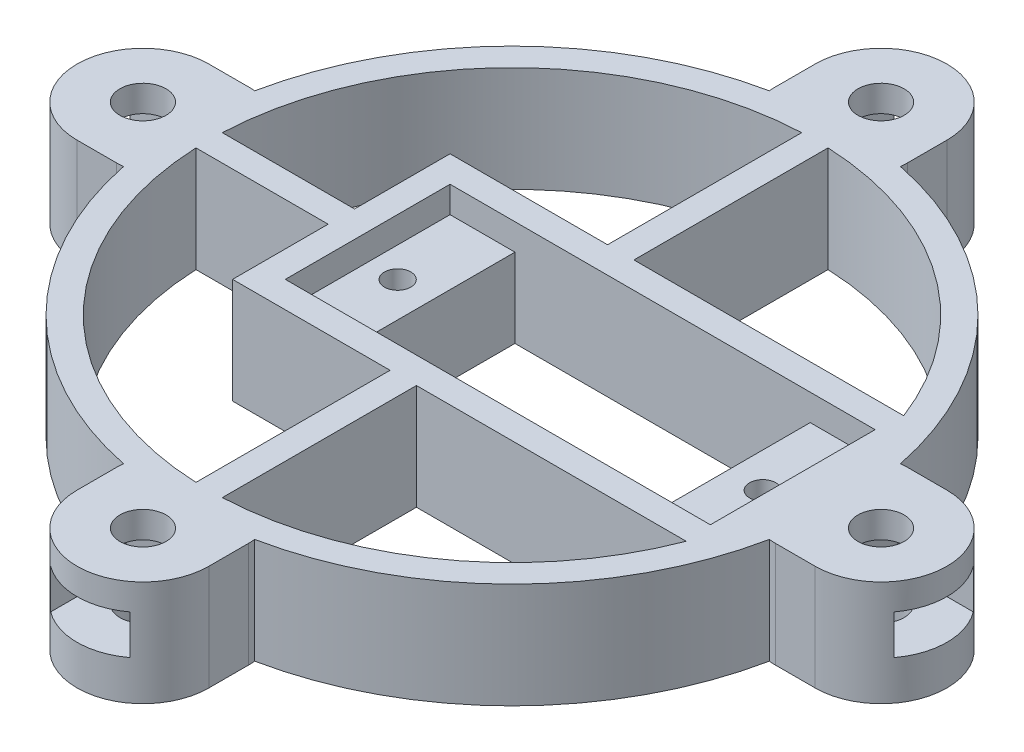
SolidWorks part; units mm, degrees
ref_plane "Front Plane" through (0, 0, 0) normal (0, 0, 1) x (1, 0, 0)
ref_plane "Top Plane" through (0, 0, 0) normal (0, 1, 0) x (1, 0, 0)
ref_plane "Right Plane" through (0, 0, 0) normal (1, 0, 0) x (0, 0, -1)
sketch "Sketch2" plane through (0, 0, 0) normal (0, 1, 0) x (1, 0, 0)
  line L0 (0, 0) -> (0, 25) construction
  circle A0 centre (0, 0) radius 25
  dimension "D1" = 50
extrude "Boss-Extrude1" add sketch "Sketch2" along normal blind 8
sketch "Sketch3" plane through (0, 8, 0) normal (0, 1, 0) x (1, 0, 0)
  line L0 (0, 25) -> (0, 0) construction
  line L1 (0, 0) -> (25, 0) construction
  line L2 (-10.95, 6.25) -> (21.3, 6.25)
  line L3 (21.3, 6.25) -> (21.3, -6.25)
  line L4 (-10.95, 6.25) -> (-10.95, -6.25)
  line L5 (-10.95, -6.25) -> (21.3, -6.25)
  circle A0 centre (0, 0) radius 25 construction
  point P12 (21.3, 0)
  point P13 (-10.95, 0)
  dimension "D1" = 32.25
  dimension "D2" = 10.95
  dimension "D3" = 12.5
extrude "Cut-Extrude1" cut sketch "Sketch3" against normal blind 2
sketch "Sketch4" plane through (0, 6, 0) normal (0, 1, 0) x (1, 0, 0)
  line L0 (5.175, 6.25) -> (5.175, -6.25) construction
  line L1 (21.3, 6.25) -> (-10.95, 6.25) construction
  line L2 (-10.95, -6.25) -> (21.3, -6.25) construction
  line L4 (-6.025, 6.25) -> (16.375, 6.25)
  line L5 (-6.025, 6.25) -> (-6.025, -6.25)
  line L6 (-6.025, -6.25) -> (16.375, -6.25)
  line L7 (16.375, 6.25) -> (16.375, -6.25)
  line L8 (-6.025, 6.25) -> (16.375, -6.25) construction
  line L9 (-6.025, -6.25) -> (16.375, 6.25) construction
  point P6 (5.175, 0)
  dimension "D1" = 22.4
extrude "Cut-Extrude2" cut sketch "Sketch4" against normal through all
sketch "Sketch6" plane through (0, 6, 0) normal (0, 1, 0) x (1, 0, 0)
  line L0 (-10.95, 0) -> (21.3, 0) construction
  line L1 (-10.95, 6.25) -> (-10.95, -6.25) construction
  line L2 (21.3, -6.25) -> (21.3, 6.25) construction
  line L3 (5.175, 6.25) -> (5.175, -6.25) construction
  line L4 (21.3, 6.25) -> (-10.95, 6.25) construction
  line L5 (-10.95, -6.25) -> (21.3, -6.25) construction
  circle A0 centre (-8.675, 0) radius 1
  circle A1 centre (19.025, 0) radius 1
  dimension "D1" = 2
  dimension "D2" = 27.7
extrude "Cut-Extrude4" cut sketch "Sketch6" against normal through all
sketch "Sketch9" plane through (0, 8, 0) normal (0, 1, 0) x (1, 0, 0)
  line L0 (-10.95, 6.25) -> (-10.95, -6.25) construction
  line L1 (-12.95, 8.25) -> (-1, 8.25)
  line L2 (-12.95, 8.25) -> (-12.95, 1)
  line L3 (-12.95, -8.25) -> (-1, -8.25)
  line L4 (-12.95, 1) -> (-22.9783, 1)
  line L6 (21.3, 6.25) -> (-10.95, 6.25) construction
  line L7 (0, 0) -> (-31.825, 0) construction
  line L8 (0, 0) -> (0, 31.7606) construction
  line L9 (-1, 22.9783) -> (-1, 8.25)
  line L10 (1, 22.9783) -> (1, 8.25)
  line L11 (-12.95, -1) -> (-22.9783, -1)
  line L12 (1, -22.9783) -> (1, -8.25)
  line L13 (-1, -22.9783) -> (-1, -8.25)
  line L14 (-12.95, -1) -> (-12.95, -8.25)
  line L15 (1, 8.25) -> (21.4695, 8.25)
  line L16 (1, -8.25) -> (21.4695, -8.25)
  arc A0 (21.4695, 8.25) -> (1, 22.9783) centre (0, 0) ccw
  arc A1 (-22.9783, -1) -> (-1, -22.9783) centre (0, 0) ccw
  arc A2 (-1, 22.9783) -> (-22.9783, 1) centre (0, 0) ccw
  arc A3 (1, -22.9783) -> (21.4695, -8.25) centre (0, 0) ccw
  dimension "D1" = 46
  dimension "D2" = 2
  dimension "D4" = 2
  dimension "D5" = 2
  dimension "D6" = 2
extrude "Cut-Extrude5" cut sketch "Sketch9" against normal through all
sketch "Sketch10" plane through (0, 8, 0) normal (0, 1, 0) x (1, 0, 0)
  line L0 (-25, 0) -> (-28, 0) construction
  line L1 (-25, -5) -> (-28, -5)
  line L2 (-25, 5) -> (-28, 5)
  line L3 (0, 0) -> (0, 32.9015) construction
  line L4 (-25, -5) -> (-28, -5)
  line L5 (-25, 5) -> (-28, 5)
  line L6 (-25, -5) -> (-28, -5)
  line L7 (-25, 5) -> (-28, 5)
  line L8 (-25, -5) -> (-28, -5)
  line L9 (-25, 5) -> (-28, 5)
  line L10 (-5, 25) -> (-5, 28)
  line L11 (5, 25) -> (5, 28)
  line L12 (-5, 25) -> (-5, 28)
  line L13 (5, 25) -> (5, 28)
  line L14 (-5, 25) -> (-5, 28)
  line L15 (5, 25) -> (5, 28)
  line L16 (-5, 25) -> (-5, 28)
  line L17 (5, 25) -> (5, 28)
  line L18 (0, 25) -> (0, 28) construction
  line L19 (25, 5) -> (28, 5)
  line L20 (25, -5) -> (28, -5)
  line L21 (25, 5) -> (28, 5)
  line L22 (25, -5) -> (28, -5)
  line L23 (25, 5) -> (28, 5)
  line L24 (25, -5) -> (28, -5)
  line L25 (25, 5) -> (28, 5)
  line L26 (25, -5) -> (28, -5)
  line L27 (25, 0) -> (28, 0) construction
  line L28 (5, -25) -> (5, -28)
  line L29 (-5, -25) -> (-5, -28)
  line L30 (5, -25) -> (5, -28)
  line L31 (-5, -25) -> (-5, -28)
  line L32 (5, -25) -> (5, -28)
  line L33 (-5, -25) -> (-5, -28)
  line L34 (5, -25) -> (5, -28)
  line L35 (-5, -25) -> (-5, -28)
  line L36 (0, -25) -> (0, -28) construction
  circle A0 centre (0, 0) radius 25 construction
  arc A1 (-25, -5) -> (-24.5, -4.9749) centre (-25, 0) ccw
  arc A2 (-28, 5) -> (-28, -5) centre (-28, 0) ccw
  arc A3 (-24.5, 4.9749) -> (-24.5, -4.9749) centre (0, 0) ccw
  arc A4 (-24.5, 4.9749) -> (-25, 5) centre (-25, 0) ccw
  arc A5 (-24.5, -4.9749) -> (-25, -5) centre (-25, 0) cw
  arc A6 (-25, 5) -> (-24.5, 4.9749) centre (-25, 0) cw
  arc A7 (-5, 25) -> (-4.9749, 24.5) centre (0, 25) ccw
  arc A8 (-25, -5) -> (-24.5, -4.9749) centre (-25, 0) ccw
  arc A9 (-24.5, 4.9749) -> (-25, 5) centre (-25, 0) ccw
  arc A10 (-24.5, -4.9749) -> (-25, -5) centre (-25, 0) cw
  arc A11 (-25, 5) -> (-24.5, 4.9749) centre (-25, 0) cw
  arc A12 (5, 28) -> (-5, 28) centre (0, 28) ccw
  arc A13 (4.9749, 24.5) -> (-4.9749, 24.5) centre (0, 0) ccw
  arc A14 (4.9749, 24.5) -> (5, 25) centre (0, 25) ccw
  arc A15 (-4.9749, 24.5) -> (-5, 25) centre (0, 25) cw
  arc A16 (5, 25) -> (4.9749, 24.5) centre (0, 25) cw
  arc A17 (-5, 25) -> (-4.9749, 24.5) centre (0, 25) ccw
  arc A18 (4.9749, 24.5) -> (5, 25) centre (0, 25) ccw
  arc A19 (-4.9749, 24.5) -> (-5, 25) centre (0, 25) cw
  arc A20 (5, 25) -> (4.9749, 24.5) centre (0, 25) cw
  arc A21 (25, 5) -> (24.5, 4.9749) centre (25, 0) ccw
  arc A22 (28, -5) -> (28, 5) centre (28, 0) ccw
  arc A23 (24.5, -4.9749) -> (24.5, 4.9749) centre (0, 0) ccw
  arc A24 (24.5, -4.9749) -> (25, -5) centre (25, 0) ccw
  arc A25 (24.5, 4.9749) -> (25, 5) centre (25, 0) cw
  arc A26 (25, -5) -> (24.5, -4.9749) centre (25, 0) cw
  arc A27 (25, 5) -> (24.5, 4.9749) centre (25, 0) ccw
  arc A28 (24.5, -4.9749) -> (25, -5) centre (25, 0) ccw
  arc A29 (24.5, 4.9749) -> (25, 5) centre (25, 0) cw
  arc A30 (25, -5) -> (24.5, -4.9749) centre (25, 0) cw
  arc A31 (5, -25) -> (4.9749, -24.5) centre (0, -25) ccw
  arc A32 (-5, -28) -> (5, -28) centre (0, -28) ccw
  arc A33 (-4.9749, -24.5) -> (4.9749, -24.5) centre (0, 0) ccw
  arc A34 (-4.9749, -24.5) -> (-5, -25) centre (0, -25) ccw
  arc A35 (4.9749, -24.5) -> (5, -25) centre (0, -25) cw
  arc A36 (-5, -25) -> (-4.9749, -24.5) centre (0, -25) cw
  arc A37 (5, -25) -> (4.9749, -24.5) centre (0, -25) ccw
  arc A38 (-4.9749, -24.5) -> (-5, -25) centre (0, -25) ccw
  arc A39 (4.9749, -24.5) -> (5, -25) centre (0, -25) cw
  arc A40 (-5, -25) -> (-4.9749, -24.5) centre (0, -25) cw
  point P6 (-26.5, 0)
  point P20 (0, 26.5)
  point P29 (26.5, 0)
  point P38 (0, -26.5)
  point P45 (0, 0)
  dimension "D2" = 5
  dimension "D3" = 4
  dimension "D1" = 3
extrude "Boss-Extrude3" add sketch "Sketch10" against normal up to surface (8 mm away) contours A5 A24 L20 A22 L19 A21 | A5 A34 L29 A32 L28 A31 | A5 A4 L2 A2 L1 A1 | A5 A14 L11 A12 L10 A7 region at (-28.4663, 8, 0) region at (0, 8, -28.4663) region at (28.4663, 8, 0) region at (0, 8, 28.4663) up to face at (8.556, 0, -14.1779)
sketch "Sketch13" plane through (0, 0, 0) normal (0, -1, 0) x (1, 0, 0)
  circle A0 centre (28, 0) radius 1.75
  circle A1 centre (0, -28) radius 1.75
  circle A2 centre (-28, 0) radius 1.75
  circle A3 centre (0, 28) radius 1.75
  point P12 (0, 0)
  dimension "D1" = 3.5
  dimension "D2" = 4
extrude "Cut-Extrude8" cut sketch "Sketch13" against normal through all
ref_plane "Plane2" through (0, 3, 0) normal (0, -1, 0) x (-1, 0, 0)
sketch "Sketch14" plane through (0, 3, 0) normal (0, -1, 0) x (-1, 0, 0)
  line L0 (0, 0) -> (-38.6509, 0) construction
  line L1 (0, 24.5359) -> (3, 26.2679)
  line L2 (-24.5359, 0) -> (-26.2679, 3)
  line L3 (-26.2679, 3) -> (-32, 3)
  line L4 (3, 26.2679) -> (3, 32)
  line L5 (-3, 32) -> (-3, 26.2679)
  line L6 (-32, -3) -> (-26.2679, -3)
  line L7 (-26.2679, -3) -> (-24.5359, 0)
  line L8 (-31.4641, 0) -> (-30.5981, -1.5) [skipped]
  line L9 (-29.7321, 3) -> (-30.5981, 1.5) [skipped]
  line L10 (-3, 26.2679) -> (0, 24.5359)
  line L11 (24.5359, 0) -> (26.2679, -3)
  line L12 (26.2679, -3) -> (32, -3)
  line L13 (32, 3) -> (26.2679, 3)
  line L14 (26.2679, 3) -> (24.5359, 0)
  line L15 (0, -24.5359) -> (-3, -26.2679)
  line L16 (-3, -26.2679) -> (-3, -32)
  line L17 (3, -32) -> (3, -26.2679)
  line L18 (3, -26.2679) -> (0, -24.5359)
  circle A0 centre (-28, 0) radius 3 construction
  arc A1 (-32, 3) -> (-32, -3) centre (-28, 0) ccw
  arc A2 (3, 32) -> (-3, 32) centre (0, 28) ccw
  circle A3 centre (0, 28) radius 3 construction
  arc A4 (32, -3) -> (32, 3) centre (28, 0) ccw
  circle A5 centre (28, 0) radius 3 construction
  arc A6 (-3, -32) -> (3, -32) centre (0, -28) ccw
  circle A7 centre (0, -28) radius 3 construction
  point P39 (0, 0)
  dimension "D1" = 6
  dimension "D2" = 10
  dimension "D3" = 4
extrude "Cut-Extrude9" cut sketch "Sketch14" against normal blind 3
